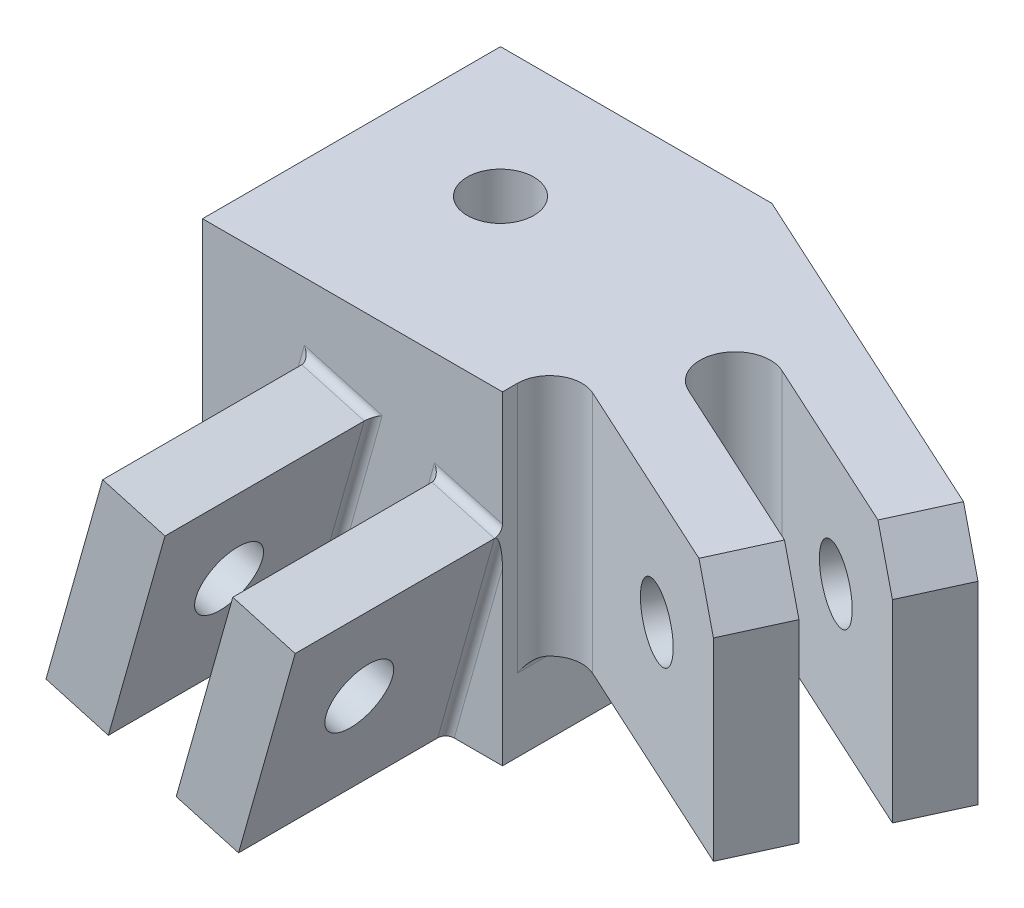
SolidWorks part; units mm, degrees
material "1060 Alloy"
ref_plane "Front Plane" through (0, 0, 0) normal (0, 0, 1) x (1, 0, 0)
ref_plane "Top Plane" through (0, 0, 0) normal (0, 1, 0) x (1, 0, 0)
ref_plane "Right Plane" through (0, 0, 0) normal (1, 0, 0) x (0, 0, -1)
sketch "Sketch1" plane through (0, 0, 0) normal (0, 1, 0) x (1, 0, 0)
  line L1 (-12.7, -16.51) -> (12.7, -16.51)
  line L2 (-12.7, -16.51) -> (-12.7, 12.7)
  line L3 (-12.7, 12.7) -> (12.7, 12.7)
  line L4 (12.7, -16.51) -> (12.7, 12.7)
  circle A0 centre (0, 0) radius 3.2639
  point P0 (0, 0)
  dimension "D2" = 6.5278
  dimension "D1" = 29.21
  dimension "D3" = 25.4
  dimension "D4" = 12.7
  dimension "D5" = 12.7
extrude "Boss-Extrude1" add sketch "Sketch1" along normal blind 31.75
sketch "Sketch2" plane through (12.7, 0, 0) normal (1, 0, 0) x (0, 0, -1)
  line L0 (12.7, 31.75) -> (12.7, 0) construction
  line L1 (12.7, 31.75) -> (-16.51, 31.75)
  line L2 (12.7, 31.75) -> (12.7, 7.6835) construction
  line L3 (12.7, 7.6835) -> (-16.51, 7.6835) construction
  line L4 (-16.51, 31.75) -> (-16.51, 7.6835) construction
  line L5 (-16.51, 31.75) -> (12.7, 31.75) construction
  line L7 (-16.51, 7.9375) -> (12.7, 7.9375)
  line L8 (12.7, 7.9375) -> (12.7, 31.75)
  line L9 (-16.51, 31.75) -> (-16.51, 7.9375)
  circle A1 centre (0, -3.429) radius 11.1125 construction
  dimension "D1" = 0.254
  dimension "D2" = 29.21
extrude "Boss-Extrude2" add sketch "Sketch2" along normal blind 33.02
ref_plane "Plane1" through (1.7219, 0, -3.7527) normal (-0.417, 0, 0.9089) x (0.9089, 0, 0.417)
sketch "Sketch3" plane through (1.7219, 0, -3.7527) normal (-0.417, 0, 0.9089) x (0.9089, 0, 0.417)
  line L1 (42.76, 36.4069) -> (53.5777, 18.2438)
  line L2 (42.76, 36.4069) -> (57.8367, 38.08)
  line L3 (57.8367, 38.08) -> (53.5777, 18.2438)
extrude "Cut-Extrude1" cut sketch "Sketch3" against normal through all and the other way through all
sketch "Sketch4" plane through (43.2353, 28.3319, 19.8382) normal (0.7809, 0.5117, 0.3583) x (0.2997, 0.1964, -0.9336)
  line L0 (6.3644, 9.0431) -> (1.1391, -13.2117) construction
  line L1 (1.1391, -13.2117) -> (7.8156, -14.7793) construction
  line L2 (7.8156, -14.7793) -> (13.0408, 7.4755) construction
  line L3 (13.0408, 7.4755) -> (6.3644, 9.0431) construction
  line L4 (9.7026, 8.2593) -> (4.4773, -13.9955) construction
  line L5 (10.4282, -3.6519) -> (3.7518, -2.0843) construction
  line L6 (23.6709, 24.9693) -> (9.5492, -35.1759)
  line L7 (9.5492, -35.1759) -> (32.6451, -40.5987)
  line L8 (32.6451, -40.5987) -> (46.7668, 19.5465)
  line L9 (46.7668, 19.5465) -> (23.6709, 24.9693)
  line L10 (10.4282, -3.6519) -> (16.6101, -5.1033) construction
  line L11 (2.6667, 21.0749) -> (-6.2607, -16.9473)
  line L12 (-6.2607, -16.9473) -> (-16.3884, -14.5694)
  line L13 (-16.3884, -14.5694) -> (-7.461, 23.4528)
  line L14 (-7.461, 23.4528) -> (2.6667, 21.0749)
  line L15 (3.7518, -2.0843) -> (-2.4301, -0.6328) construction
  line L16 (13.0714, 7.4945) -> (6.3455, 9.0737)
  line L17 (6.3455, 9.0737) -> (1.1086, -13.2306)
  line L18 (1.1086, -13.2306) -> (7.8345, -14.8098)
  line L19 (7.8345, -14.8098) -> (13.0714, 7.4945)
  dimension "D1" = 22.86
  dimension "D2" = 6.35
  dimension "D3" = 6.35
  dimension "D4" = 0.0254
extrude "Cut-Extrude2" cut sketch "Sketch4" against normal blind 24.13
sketch "Sketch6" plane through (0, 0, 16.51) normal (0, 0, 1) x (1, 0, 0)
  line L0 (-12.7, 31.75) -> (-12.7, 0) construction
  line L1 (-12.7, 0) -> (11.1522, 0)
  line L2 (-12.7, 0) -> (-12.7, 5.5537)
  line L3 (-12.7, 0) -> (12.7, 0) construction
  line L4 (12.7, 5.4937) -> (12.7, 20.828) construction
  line L6 (12.7, 20.828) -> (10.5906, 21.4223)
  line L7 (-2.1714, 25.0179) -> (-8.0263, 4.2369)
  line L8 (-8.0263, 4.2369) -> (-12.7, 5.5537)
  line L9 (-1.752, 2.997) -> (3.9651, 23.289) construction
  line L10 (4.849, 1.1372) -> (10.5661, 21.4292) construction
  line L11 (3.9407, 23.2959) -> (-2.1714, 25.0179)
  line L12 (4.8734, 1.1303) -> (10.5906, 21.4223)
  line L13 (-1.7765, 3.0039) -> (3.9407, 23.2959)
  line L14 (-1.752, 2.997) -> (4.2045, 24.1388) construction
  line L15 (10.5906, 21.4223) -> (3.9407, 23.2959) construction
  line L16 (-1.7765, 3.0039) -> (4.1801, 24.1457) construction
  line L17 (4.849, 1.1372) -> (10.8056, 22.279) construction
  line L18 (4.8734, 1.1303) -> (10.83, 22.2721) construction
  line L19 (-1.7765, 3.0039) -> (4.8734, 1.1303)
  line L20 (-1.4723, 3.9897) -> (-1.2761, 2.8629) construction
  line L21 (12.7, 7.9375) -> (12.7, 0) construction
  line L24 (12.7, 20.828) -> (16.7026, 19.7003)
  line L25 (16.7026, 19.7003) -> (11.1522, 0)
  dimension "D3" = 21.082
  dimension "D4" = 20.828
  dimension "D5" = 1.0313
  dimension "D6" = 6.35
  dimension "D7" = 21.59
  dimension "D8" = 6.35
  dimension "D1" = 0.0254
  dimension "D2" = 0.0254
extrude "Boss-Extrude3" add sketch "Sketch6" along normal blind 20.32
sketch "Sketch24" plane through (0, 0, 0) normal (0, -1, 0) x (1, 0, 0)
  line L0 (11.1522, 36.83) -> (11.1522, 16.51) construction
  line L1 (-12.7, 36.83) -> (11.1522, 36.83)
  line L2 (-12.7, 36.83) -> (-12.7, 11.43)
  line L3 (-12.7, 11.43) -> (11.1522, 11.43)
  line L4 (11.1522, 36.83) -> (11.1522, 11.43)
  dimension "D1" = 25.4
sketch "Sketch7" plane through (-8.542, 2.4066, 0) normal (-0.9625, 0.2712, 0) x (0, 0, 1)
  line L0 (0, 0) -> (27.8986, 0) construction
  line L1 (27.8986, 13.7258) -> (27.8986, 0) construction
  circle A0 centre (27.8986, 13.7258) radius 3.2639
  dimension "D1" = 6.5278
  dimension "D2" = 27.8986
  dimension "D3" = 13.7258
extrude "Cut-Extrude3" cut sketch "Sketch7" against normal through all
sketch "Sketch8" plane through (7.2301, 0, -15.7573) normal (0.417, 0, -0.9089) x (-0.9089, 0, -0.417)
  line L0 (0, 0) -> (-37.1321, 0) construction
  line L1 (-37.1321, 0) -> (-37.1321, 20.7519) construction
  circle A0 centre (-37.1321, 20.7519) radius 3.2639
  dimension "D1" = 6.5278
  dimension "D2" = 37.1321
  dimension "D3" = 20.7519
extrude "Cut-Extrude4" cut sketch "Sketch8" against normal through all
sketch "Sketch9" plane through (-0.9263, 0, 2.0188) normal (-0.417, 0, 0.9089) x (0.9089, 0, 0.417)
  line L0 (34.748, 31.75) -> (17.448, 31.75) construction
  line L1 (17.448, 31.75) -> (31.6305, 7.9375) construction
  line L5 (48.4397, 26.8706) -> (45.5336, 31.75) construction
  line L6 (45.5336, 31.75) -> (34.748, 31.75) construction
  line L7 (34.748, 31.75) -> (17.448, 31.75)
  line L8 (17.448, 31.75) -> (31.6305, 7.9375)
  line L9 (48.4397, 26.8706) -> (48.4397, 7.9375) construction
  line L10 (48.4397, 7.9375) -> (34.748, 7.9375) construction
  line L11 (34.748, 7.9375) -> (31.6305, 7.9375) construction
  line L12 (48.4397, 26.8706) -> (45.5336, 31.75)
  line L13 (45.5336, 31.75) -> (34.748, 31.75)
  line L14 (48.4397, 26.8706) -> (48.4397, 7.9375)
  line L15 (48.4397, 7.9375) -> (34.748, 7.9375)
  line L16 (34.748, 7.9375) -> (31.6305, 7.9375)
  circle A2 centre (37.1321, 20.7519) radius 3.2639
  arc A3 (34.748, 22.9812) -> (34.748, 18.5227) centre (37.1321, 20.7519) ccw construction
extrude "Boss-Extrude4" add sketch "Sketch9" against normal up to surface (2.5915 mm away) up to face at (4.824, 15.228, 16.51)
sketch "Sketch11" plane through (0, 0, 16.51) normal (0, 0, -1) x (-1, 0, 0)
  line L3 (-12.7, 5.4937) -> (-12.7, 7.9375)
  line L4 (-12.7, 7.9375) -> (-13.3885, 7.9375)
  line L5 (-13.3885, 7.9375) -> (-12.7, 5.4937)
  line L6 (-12.7, 5.4937) -> (-12.7, 7.9375)
  line L7 (-12.7, 7.9375) -> (-13.3885, 7.9375)
  line L8 (-13.3885, 7.9375) -> (-12.7, 5.4937)
  dimension "D1" = 0
extrude "Boss-Extrude5" add sketch "Sketch11" along normal up to surface (29.21 mm away) up to face at (13.2695, 13.8906, -12.7)
sketch "Sketch13" plane through (0, 7.9375, 0) normal (0, -1, 0) x (1, 0, 0)
  line L0 (45.72, 1.9035) -> (37.5636, 19.6796)
  line L1 (43.1, 22.2199) -> (27.8223, 15.2099) construction
  line L2 (37.5636, 19.6796) -> (21.5153, 12.3159)
  line L3 (21.5153, 12.3159) -> (29.6717, -5.4601)
  line L4 (29.6717, -5.4601) -> (45.72, 1.9035)
extrude "Boss-Extrude6" add sketch "Sketch13" against normal blind 1.27
sketch "Sketch14" plane through (0, 31.75, 0) normal (0, 1, 0) x (1, 0, 0)
  line L0 (25.0244, 12.7) -> (23.0884, 8.4808)
  line L1 (23.0884, 8.4808) -> (21.9579, 12.7)
  line L2 (25.0244, 12.7) -> (-12.7, 12.7) construction
  line L3 (21.9579, 12.7) -> (25.0244, 12.7)
  dimension "D1" = 75
sketch "Sketch15" plane through (0, 7.9375, 0) normal (0, -1, 0) x (1, 0, 0)
  line L0 (40.6286, -12.7) -> (35.9787, -2.5662)
  line L1 (35.9787, -2.5662) -> (33.2634, -12.7)
  line L2 (40.6286, -12.7) -> (13.3885, -12.7) construction
  line L3 (33.2634, -12.7) -> (40.6286, -12.7)
  dimension "D1" = 75
loft "Cut-Loft1" cut profiles "Sketch14", "Sketch15" connector at (23.0884, 31.75, -8.4808) connector at (35.9787, 7.9375, -2.5662)
sketch "Sketch19" plane through (-0.9263, 0, 2.0188) normal (-0.417, 0, 0.9089) x (0.9089, 0, 0.417)
  line L0 (48.4203, 26.9032) -> (48.4203, 14.1419) construction
  line L1 (48.4397, 7.9375) -> (48.4203, 7.9375)
  line L2 (48.4397, 7.9375) -> (48.4397, 30.9082)
  line L3 (48.4397, 30.9082) -> (48.4203, 30.9082)
  line L4 (48.4203, 7.9375) -> (48.4203, 30.9082)
extrude "Cut-Extrude7" cut sketch "Sketch19" against normal through all
sketch "Sketch21" plane through (7.2301, 0, -15.7573) normal (0.417, 0, -0.9089) x (-0.9089, 0, -0.417)
  line L0 (-48.4203, 26.9032) -> (-48.4203, 14.1419) construction
  line L1 (-48.4203, 26.9032) -> (-45.5336, 31.75) construction
  line L2 (-48.4203, 26.9032) -> (-48.4203, 14.1419)
  line L3 (-48.4203, 26.9032) -> (-45.5336, 31.75)
  line L4 (-45.2503, 31.75) -> (-45.5336, 31.75)
  line L6 (-48.4203, 14.1419) -> (-48.4203, 7.9375)
  line L7 (-48.4203, 7.9375) -> (-42.3483, 7.9375)
  line L8 (-42.3483, 7.9375) -> (-42.3483, 31.75)
  line L9 (-42.3483, 31.75) -> (-45.2503, 31.75)
  line L10 (-45.2503, 31.75) -> (-45.2503, 12.2538)
  line L11 (-45.2503, 12.2538) -> (-48.4203, 14.1419)
  line L12 (-48.4203, 14.1419) -> (-48.4203, 7.9375)
  line L13 (-48.4203, 7.9375) -> (-42.3483, 7.9375)
  line L14 (-42.3483, 7.9375) -> (-42.3483, 31.75)
  line L15 (-42.3483, 31.75) -> (-45.2503, 31.75)
  dimension "D1" = 0
extrude "Boss-Extrude9" add sketch "Sketch21" against normal up to surface (6.3246 mm away) up to face at (35.3749, 20.7519, 4.1154)
sketch "Sketch22" plane through (4.5925, 0, -10.0089) normal (-0.417, 0, 0.9089) x (0.9089, 0, 0.417)
  line L0 (48.4203, 7.9375) -> (48.4203, 14.1419)
  line L1 (48.4203, 7.9375) -> (48.4203, 26.9032) construction
  line L2 (48.4203, 14.1419) -> (45.2503, 12.2538) construction
  line L3 (48.4203, 14.1419) -> (45.2503, 12.2538)
  line L4 (45.2503, 12.2538) -> (45.2503, 7.9375)
  line L5 (45.2503, 7.9375) -> (48.4203, 7.9375)
  line L6 (40.1355, 9.2075) -> (45.2503, 12.2538) construction
  line L7 (40.1355, 9.2075) -> (45.2503, 12.2538) construction
extrude "Boss-Extrude10" add sketch "Sketch22" along normal up to surface (13.2334 mm away) up to face at (33.8756, 21.2556, 17.9874)
sketch "Sketch25" plane through (0, 31.75, 0) normal (0, 1, 0) x (1, 0, 0)
  circle A0 centre (0, 0) radius 3.2639 construction
  circle A1 centre (0, 0) radius 3.2639
extrude "Boss-Extrude13" add sketch "Sketch25" against normal offset from surface (18.0975 mm away) 13.6525 up to face at (3.7174, 0, 13.5467)
sketch "Sketch26" plane through (0, 0, 0) normal (0, -1, 0) x (1, 0, 0)
  circle A0 centre (0, 0) radius 3.2639
  dimension "D1" = 6.5278
extrude "Cut-Extrude8" cut sketch "Sketch26" against normal through all
sketch "Sketch32" plane through (0, 0, 36.83) normal (0, 0, 1) x (1, 0, 0)
  line L4 (5.0887, 1.8943) -> (4.555, 0)
  line L5 (-12.7, 0) -> (11.1522, 0) construction
  line L6 (-1.5612, 3.7679) -> (-2.6228, 0)
  line L7 (-2.6228, 0) -> (4.555, 0)
  line L8 (-1.5612, 3.7679) -> (5.0887, 1.8943)
extrude "Cut-Extrude11" cut sketch "Sketch32" against normal up to surface (20.32 mm away) up to face at (4.824, 15.228, 16.51)
sketch "Sketch33" plane through (0, 0, 16.51) normal (0, 0, 1) x (1, 0, 0)
  line L0 (12.7, 5.4937) -> (12.7, 0) construction
  line L1 (11.1522, 0) -> (12.7, 5.4937) construction
  line L2 (11.1522, 0) -> (12.7, 0) construction
  line L3 (12.7, 5.4937) -> (12.7, 0)
  line L4 (11.1522, 0) -> (12.7, 5.4937)
  line L5 (11.1522, 0) -> (12.7, 0)
extrude "Cut-Extrude12" cut sketch "Sketch33" against normal through all
sketch "Sketch34" plane through (0, 0, 36.83) normal (0, 0, 1) x (1, 0, 0)
  line L2 (-8.0263, 4.2369) -> (-9.22, 0)
  line L3 (-12.7, 5.5537) -> (-8.0263, 4.2369)
  line L4 (-12.7, 5.5537) -> (-12.7, 0)
  line L5 (-12.7, 5.5537) -> (-12.7, 0) construction
  line L6 (-12.7, 0) -> (-2.6228, 0) construction
  line L7 (-12.7, 0) -> (-9.22, 0)
  line L8 (-12.7, 0) -> (11.1522, 0) construction
extrude "Cut-Extrude13" cut sketch "Sketch34" against normal up to surface (20.32 mm away) up to face at (4.7269, 14.8835, 16.51)
sketch "Sketch35" plane through (0, 31.75, 0) normal (0, 1, 0) x (1, 0, 0)
  line L0 (14.932, -9.2952) -> (40.4587, -21.008) construction
  line L2 (14.932, -9.2952) -> (30.6558, -16.51)
  line L4 (11.6216, -16.51) -> (30.6558, -16.51)
  line L5 (11.6216, -16.51) -> (14.932, -9.2952)
extrude "Boss-Extrude15" add sketch "Sketch35" against normal up to surface up to face at (20.4004, 19.8438, 14.3813)
sketch "Sketch38" plane through (0, 31.75, 0) normal (0, 1, 0) x (1, 0, 0)
  line L0 (35.8518, 2.6244) -> (33.9993, 14.4404)
  line L1 (48.6151, -3.2319) -> (23.0884, 8.4808) construction
  line L2 (33.9993, 14.4404) -> (5.3027, 16.6416)
  line L3 (35.8518, 2.6244) -> (5.3027, 16.6416)
  line L4 (23.0884, 8.4808) -> (35.9787, 2.5662) construction
extrude "Cut-Extrude15" cut sketch "Sketch38" against normal through all
sketch "Sketch39" plane through (0, 31.75, 0) normal (0, 1, 0) x (1, 0, 0)
  line L2 (35.8518, 2.6244) -> (35.9787, 2.5662)
  line L3 (35.9787, 2.5662) -> (35.6947, 3.6262)
  line L4 (35.6947, 3.6262) -> (35.8518, 2.6244)
extrude "Cut-Extrude16" cut sketch "Sketch39" against normal through all
sketch "Sketch40" plane through (0, 31.75, 0) normal (0, 1, 0) x (1, 0, 0)
  line L0 (30.6558, -16.51) -> (16.7026, -10.1077)
  line L1 (-12.7, -16.51) -> (30.6558, -16.51) construction
  line L2 (30.6558, -16.51) -> (40.4587, -21.008) construction
  line L3 (16.7026, -16.51) -> (16.7026, -10.1077)
  line L4 (16.7026, -16.51) -> (30.6558, -16.51)
extrude "Cut-Extrude17" cut sketch "Sketch40" against normal through all
sketch "Sketch41" plane through (0, 31.75, 0) normal (0, 1, 0) x (1, 0, 0)
  line L0 (34.7779, -3.8414) -> (31.8966, -10.1207)
  line L1 (41.0713, -6.7291) -> (32.6537, -2.8667) construction
  line L2 (31.8966, -10.1207) -> (34.7779, -3.8414) construction
  line L3 (31.8966, -10.1207) -> (45.72, -16.4635)
  line L4 (45.72, -16.4635) -> (48.6012, -10.1842)
  line L5 (48.6012, -10.1842) -> (34.7779, -3.8414)
extrude "Cut-Extrude18" cut sketch "Sketch41" against normal through all
sketch "Sketch42" plane through (0, 31.75, 0) normal (0, 1, 0) x (1, 0, 0)
  line L0 (24.2023, 1.0111) -> (21.3211, -5.2682) construction
  line L1 (24.2023, 1.0111) -> (21.3211, -5.2682)
  line L2 (31.8966, -10.1207) -> (21.3211, -5.2682)
  line L3 (34.7779, -3.8414) -> (24.2023, 1.0111)
  line L4 (31.8966, -10.1207) -> (34.7779, -3.8414)
  line L11 (-12.7, -16.51) -> (16.7026, -16.51)
  line L12 (16.7026, -16.51) -> (16.7026, -10.1077)
  line L13 (16.7026, -10.1077) -> (40.4587, -21.008)
  line L14 (40.4587, -21.008) -> (43.0963, -15.2596)
  line L15 (43.0963, -15.2596) -> (31.8966, -10.1207)
  line L16 (31.8966, -10.1207) -> (34.7779, -3.8414)
  line L17 (34.7779, -3.8414) -> (45.9775, -8.9803)
  line L18 (34.7779, -3.8414) -> (45.9775, -8.9803)
  line L19 (45.9775, -8.9803) -> (48.6151, -3.2319)
  line L20 (13.8931, 12.7) -> (-12.7, 12.7)
  line L21 (-12.7, 12.7) -> (-12.7, -16.51)
  line L22 (-12.7, -16.51) -> (16.7026, -16.51)
  line L23 (16.7026, -16.51) -> (16.7026, -10.1077)
  line L24 (16.7026, -10.1077) -> (40.4587, -21.008)
  line L25 (40.4587, -21.008) -> (43.0963, -15.2596)
  line L26 (43.0963, -15.2596) -> (31.8966, -10.1207)
  line L27 (31.8966, -10.1207) -> (34.7779, -3.8414)
  line L31 (13.8931, 12.7) -> (-12.7, 12.7)
  line L38 (45.9775, -8.9803) -> (48.6151, -3.2319)
  line L39 (48.6151, -3.2319) -> (13.8931, 12.7)
  line L40 (48.6151, -3.2319) -> (13.8931, 12.7)
  line L41 (-12.7, 12.7) -> (-12.7, -16.51)
  line M17 (31.8966, -10.1207) -> (34.7779, -3.8414)
  dimension "D1" = 0
extrude "Cut-Extrude19" cut sketch "Sketch42" against normal up to surface (26.4666 mm away) contours L3 L1 L2 M17 region at (28.0495, 31.75, 4.5548) up to face at (26.9874, 17.0137, 4.0675)
sketch "Sketch44" plane through (0, 0, 16.51) normal (0, 0, 1) x (1, 0, 0)
  line L0 (16.7026, 19.7003) -> (13.3885, 7.9375)
  line L1 (13.3885, 7.9375) -> (16.7026, 7.9375)
  line L2 (16.7026, 7.9375) -> (16.7026, 19.7003)
extrude "Cut-Extrude20" cut sketch "Sketch44" against normal up to surface (7.923 mm away) up to face at (32.0058, 21.2556, 17.1294)
sketch "Sketch45" plane through (0, 31.75, 0) normal (0, 1, 0) x (1, 0, 0)
  line L0 (16.7026, -10.1077) -> (16.7026, -16.51) construction
  line L1 (16.7026, -10.1077) -> (40.4587, -21.008) construction
  line L2 (16.7026, -15.0578) -> (16.7026, -16.51)
  line L3 (21.2017, -12.1721) -> (40.4587, -21.008)
  line L4 (16.7026, -15.0578) -> (16.7026, -10.1077)
  line L5 (16.7026, -10.1077) -> (21.2017, -12.1721)
  arc A0 (16.7026, -15.0578) -> (21.2017, -12.1721) centre (19.8776, -15.0578) cw
  line M10 (16.7026, -16.51) -> (16.7026, -10.1077)
  line M11 (16.7026, -10.1077) -> (40.4587, -21.008)
  dimension "D1" = 3.175
extrude "Boss-Extrude16" add sketch "Sketch45" against normal up to surface (23.8125 mm away) contours A0 M10 M11 region at (17.7847, 31.75, 11.7948) up to face at (30.5215, 7.9375, 4.5065)
sketch "Sketch49" plane through (0, 31.75, 0) normal (0, 1, 0) x (1, 0, 0)
  line L0 (24.2023, 1.0111) -> (21.3211, -5.2682)
  line L1 (21.3211, -5.2682) -> (30.4599, -9.4615)
  line L2 (30.4599, -9.4615) -> (33.3412, -3.1822)
  line L3 (33.3412, -3.1822) -> (24.2023, 1.0111)
extrude "Cut-Extrude22" cut sketch "Sketch49" against normal through all
sketch "Sketch52" plane through (0, 0, 0) normal (0, -1, 0) x (1, 0, 0)
  line L0 (-2.6228, 16.51) -> (11.1522, 16.51) construction
  line L1 (11.1522, 36.83) -> (11.1522, -12.7) construction
sketch "Sketch56" plane through (0, 7.9375, 0) normal (0, -1, 0) x (1, 0, 0)
  line L0 (13.3885, 8.587) -> (16.7026, 10.1077)
  line L1 (16.7026, 10.1077) -> (16.7026, 15.0578)
  line L2 (16.7026, 10.1077) -> (16.7026, 15.0578) construction
  line L3 (13.3885, 8.587) -> (13.3885, 15.0578)
  line L4 (13.3885, 15.0578) -> (16.7026, 15.0578)
  arc A0 (16.7026, 15.0578) -> (21.2017, 12.1721) centre (19.8776, 15.0578) ccw construction
extrude "Boss-Extrude20" add sketch "Sketch56" against normal blind 17.018
sketch "Sketch58" plane through (0, 0, 15.0578) normal (0, 0, 1) x (1, 0, 0)
  line L3 (16.7026, 19.7003) -> (13.3885, 7.9375)
  line L4 (13.3885, 7.9375) -> (16.7026, 7.9375)
  line L5 (16.7026, 7.9375) -> (16.7026, 19.7003)
  line L6 (16.7026, 19.7003) -> (13.3885, 7.9375)
  line L7 (13.3885, 7.9375) -> (16.7026, 7.9375)
  line L8 (16.7026, 7.9375) -> (16.7026, 19.7003)
  dimension "D1" = 0
extrude "Boss-Extrude21" add sketch "Sketch58" along normal up to surface (1.4522 mm away) up to face at (1.3077, 15.2936, 16.51)
sketch "Sketch59" plane through (0, 0, 16.51) normal (0, 0, 1) x (1, 0, 0)
  line L0 (16.7026, 7.9375) -> (16.7026, 0)
  line L1 (-2.6228, 0) -> (11.1522, 0) construction
  line L2 (16.7026, 0) -> (4.2647, 0)
  line L3 (4.2647, 0) -> (13.3885, 7.9375)
  line L4 (13.3885, 7.9375) -> (16.7026, 7.9375)
extrude "Boss-Extrude22" add sketch "Sketch59" against normal up to surface (29.21 mm away) up to face at (6.746, 13.2292, -12.7)
sketch "Sketch60" plane through (0, 7.9375, 0) normal (0, 1, 0) x (1, 0, 0)
  line L3 (13.8931, 12.7) -> (16.7026, 11.4109)
  line L4 (16.7026, 11.4109) -> (16.7026, 12.7)
  line L5 (16.7026, 12.7) -> (13.8931, 12.7)
  line L6 (13.8931, 12.7) -> (16.7026, 11.4109)
  line L7 (16.7026, 11.4109) -> (16.7026, 12.7)
  line L8 (16.7026, 12.7) -> (13.8931, 12.7)
  dimension "D1" = 0
extrude "Cut-Extrude23" cut sketch "Sketch60" against normal blind 17.018
sketch "Sketch62" plane through (19.6098, 0, 8.9978) normal (0.9089, 0, 0.417) x (0.417, 0, -0.9089)
  line L4 (4.1034, 31.75) -> (4.1034, 7.9375)
  line L5 (4.1034, 7.9375) -> (11.0122, 7.9375)
  line L6 (11.0122, 7.9375) -> (11.0122, 31.75)
  line L7 (11.0122, 31.75) -> (4.1034, 31.75)
  line L8 (4.1034, 31.75) -> (4.1034, 7.9375)
  line L9 (4.1034, 7.9375) -> (11.0122, 7.9375)
  line L10 (11.0122, 7.9375) -> (11.0122, 31.75)
  line L11 (11.0122, 31.75) -> (4.1034, 31.75)
  dimension "D1" = 0
extrude "Boss-Extrude23" add sketch "Sketch62" along normal blind 4.826
sketch "Sketch64" plane through (0, 31.75, 0) normal (0, 1, 0) x (1, 0, 0)
  line L0 (28.5886, -1.0015) -> (25.7074, -7.2808) construction
  circle A0 centre (27.148, -4.1412) radius 3.4544
extrude "Cut-Extrude25" cut sketch "Sketch64" against normal through all
fillet "Fillet4" radius 0.7937 1 edges at (16.7026, 7.9375, 1.8234)
sketch "Sketch67" plane through (0, 0, 36.83) normal (0, 0, 1) x (1, 0, 0)
  line L0 (11.1522, 0) -> (-7.7218, 5.3176)
  line L1 (-2.1714, 25.0179) -> (-9.22, 0) construction
  line L2 (-7.7218, 5.3176) -> (-9.22, 0)
  line L3 (-9.22, 0) -> (11.1522, 0)
  line L4 (3.9407, 23.2959) -> (-2.1714, 25.0179) construction
extrude "Cut-Extrude27" cut sketch "Sketch67" against normal up to surface (20.32 mm away) up to face at (1.3077, 15.2936, 16.51)
fillet "Fillet6" radius 0.7937 6 edges at (13.6466, 20.5613, 16.51) (7.8154, 11.5722, 16.51) (-4.6658, 4.4566, 16.51) (1.1655, 13.4457, 16.51) (0.8846, 24.1569, 16.51) (-4.9466, 15.1678, 16.51)
fillet "Fillet7" radius 0.7937 1 edges at (7.7142, 0.9686, 16.51)
fillet "Fillet8" radius 0.7937 1 edges at (13.9274, 9.8501, 16.51)
equation "\"0.045n\"=0.04"
